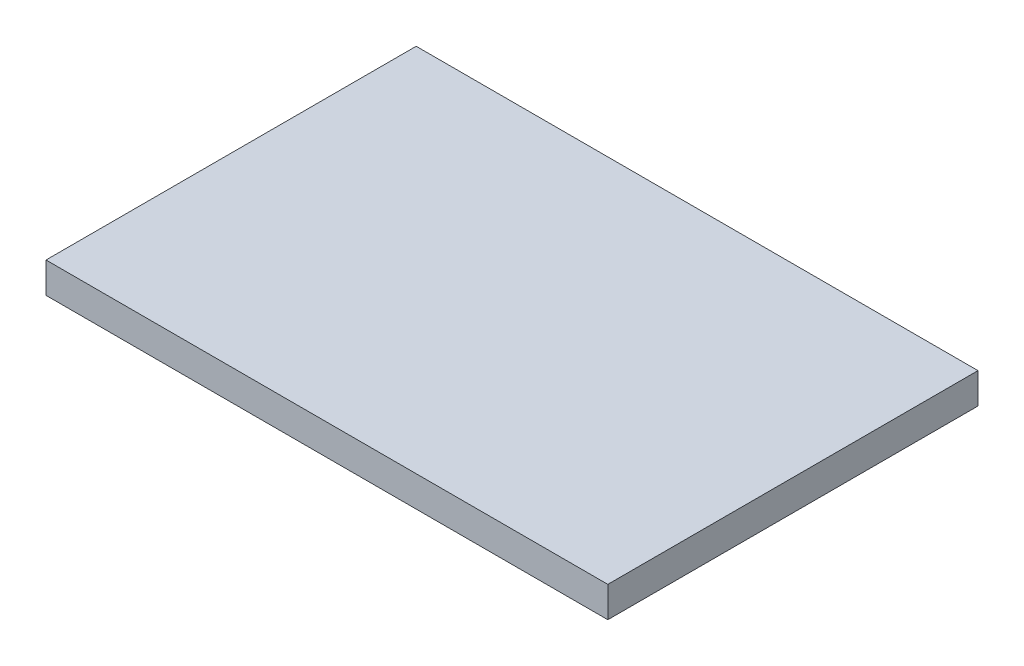
SolidWorks part; units mm, degrees
ref_plane "Front Plane" through (0, 0, 0) normal (0, 0, 1) x (1, 0, 0)
ref_plane "Top Plane" through (0, 0, 0) normal (0, 1, 0) x (1, 0, 0)
ref_plane "Right Plane" through (0, 0, 0) normal (1, 0, 0) x (0, 0, -1)
sketch "Sketch1" plane through (0, 0, 0) normal (0, 1, 0) x (1, 0, 0)
  line L1 (-366.5, 241.5) -> (366.5, 241.5)
  line L2 (-366.5, 241.5) -> (-366.5, -241.5)
  line L3 (-366.5, -241.5) -> (366.5, -241.5)
  line L4 (366.5, 241.5) -> (366.5, -241.5)
  line L5 (-366.5, 241.5) -> (366.5, -241.5) construction
  line L6 (-366.5, -241.5) -> (366.5, 241.5) construction
  point P0 (0, 0)
  dimension "D1" = 733
  dimension "D2" = 483
extrude "Boss-Extrude1" add sketch "Sketch1" along normal blind 40
